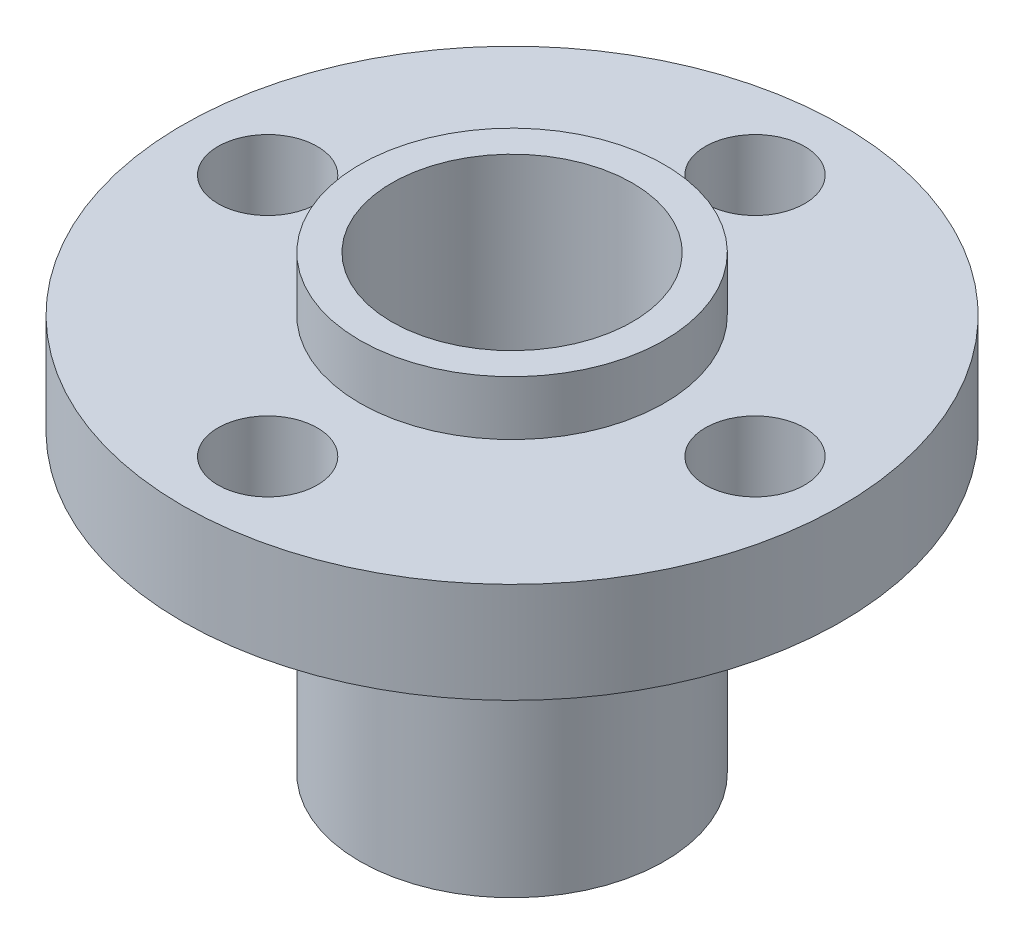
SolidWorks part; units mm, degrees
ref_plane "Спереди" through (0, 0, 0) normal (0, 0, 1) x (1, 0, 0)
ref_plane "Сверху" through (0, 0, 0) normal (0, 1, 0) x (1, 0, 0)
ref_plane "Справа" through (0, 0, 0) normal (1, 0, 0) x (0, 0, -1)
sketch "Эскиз1" plane through (0, 0, 0) normal (0, 1, 0) x (1, 0, 0)
  circle A0 centre (0, 0) radius 4
  circle A1 centre (0, 0) radius 10.955
  circle A2 centre (0, 0) radius 5.06
  circle A3 centre (0, 8.0753) radius 1.65
  circle A4 centre (8.1, -0.0247) radius 1.65
  circle A5 centre (0, -8.1247) radius 1.65
  circle A6 centre (-8.1, -0.0247) radius 1.65
  point P16 (0, -0.0247)
  dimension "D1" = 21.91
  dimension "D2" = 10.12
  dimension "D3" = 8
  dimension "D4" = 3.3
  dimension "D6" = 16.2
  dimension "D5" = 4
extrude "Бобышка-Вытянуть1" add sketch "Эскиз1" along normal blind 15 contours A2 A0 region at (-4.9169, 0, 0)
extrude "Бобышка-Вытянуть2" add sketch "Эскиз1<3>" along normal blind 3.34 from offset 9.85 contours A1 A6 A5 A4 A3 A2 region at (-10.6451, 0, 0)
sketch "Эскиз1<3>" plane through (0, 0, 0) normal (0, 1, 0) x (1, 0, 0) same geometry as "Эскиз1"
sketch "Sketch1" plane through (0, 13.19, 0) normal (0, 1, 0) x (1, 0, 0)
  line L1 (-8.1, -2.5247) -> (-11.8688, -2.5247)
  line L3 (-8.1, 2.4753) -> (-11.8688, 2.4753)
  line L4 (-11.8688, -2.5247) -> (-11.8688, 2.4753)
  line L5 (8.1, -2.5247) -> (12.756, -2.5247)
  line L7 (8.1, 2.4753) -> (12.756, 2.4753)
  line L8 (12.756, -2.5247) -> (12.756, 2.4753)
  arc A2 (-8.1, -2.5247) -> (-8.1, 2.4753) centre (-8.1, -0.0247) ccw
  arc A3 (8.1, 2.4753) -> (8.1, -2.5247) centre (8.1, -0.0247) ccw
  circle A4 centre (-8.1, -0.0247) radius 1.65 construction
  circle A5 centre (8.1, -0.0247) radius 1.65 construction
  dimension "D1" = 5
  dimension "D2" = 5
extrude "Extrude1" [suppressed] cut sketch "Sketch1" against normal up to next
chamfer "Фаска1" [suppressed] distance 0.1 angle 45
